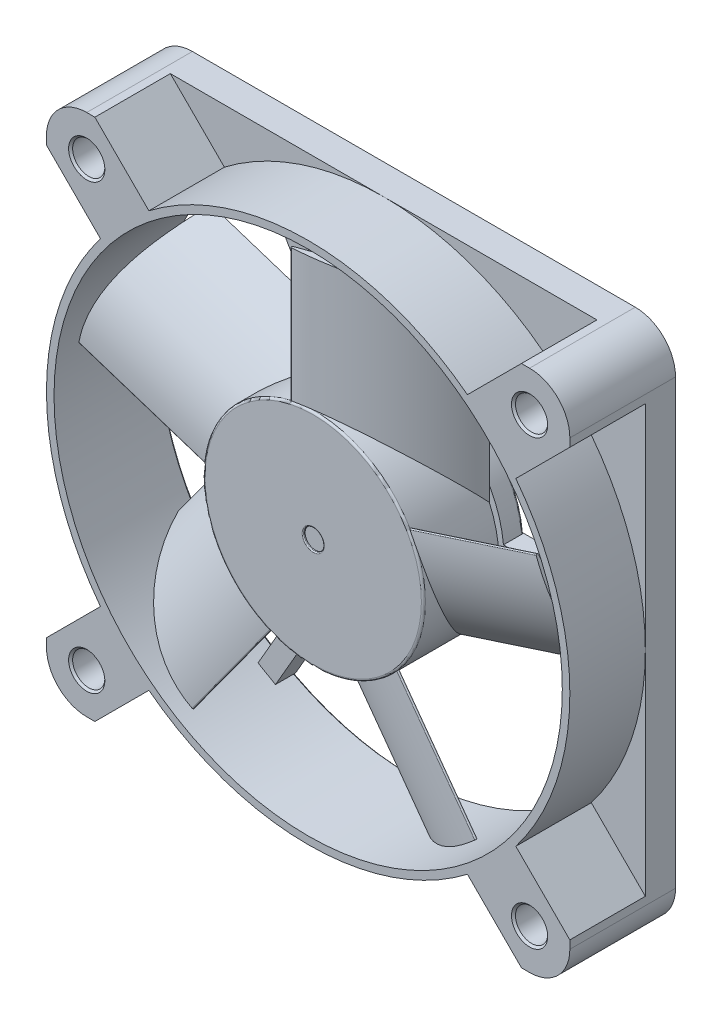
SolidWorks part; units mm, degrees
note: '?' marks a value the reader was unsure of.
material "ABS"
ref_plane "Спереди" through (0, 0, 0) normal (0, 0, 1) x (1, 0, 0)
ref_plane "Сверху" through (0, 0, 0) normal (0, 1, 0) x (1, 0, 0)
ref_plane "Справа" through (0, 0, 0) normal (1, 0, 0) x (0, 0, -1)
sketch "Эскиз1" plane through (0, 0, 0) normal (0, 0, 1) x (1, 0, 0)
  circle A0 centre (0, 0) radius 10.95
  dimension "D1" = 21.9
extrude "Вытянуть1" add sketch "Эскиз1" along normal blind 7.5
fillet "Скругление1" radius 0.2 1 edges at (10.95, 0, 7.5)
sketch "Эскиз2" plane through (0, 0, 7.5) normal (0, 0, 1) x (1, 0, 0)
  circle A0 centre (0, 0) radius 1
  dimension "D1" = 2
extrude "Вырез-Вытянуть1" cut sketch "Эскиз2" against normal blind 0.2
fillet "Скругление2" radius 0.1 1 edges at (1, 0, 7.5)
ref_plane "Плоскость1" through (0, 25, 0) normal (0, 1, 0) x (-1, 0, 0)
sketch "Эскиз3" plane through (0, 25, 0) normal (0, 1, 0) x (-1, 0, 0)
  line L0 (-10.95, 7.3) -> (10.95, 7.3) construction
  line L1 (-10.95, 0) -> (10.95, 0) construction
  arc A0 (2.2956, 7.3507) -> (-10, 0) centre (1.7146, -5.6363) ccw
  arc A1 (2.3134, 7.1533) -> (-10, 0) centre (7.6697, -16.2413) ccw
  arc A2 (2.2956, 7.3507) -> (2.3134, 7.1533) centre (2.2911, 7.2508) cw
  point P11 (3, 7.3)
  dimension "D3" = 13
  dimension "D4" = 24
  dimension "D5" = 0.1
  dimension "D1" = 13
  dimension "D2" = 3
extrude "Вытянуть2" add sketch "Эскиз3" against normal up to surface (14.2972 mm away)
ref_axis "Ось1" through (0, 0, 7.3) along (0, 0, -1)?
pattern_circular "Круговой массив1" count 5 over 360 about axis through (0, 0, 0) along (0, 0, 1) of "Вытянуть2"
sketch "Эскиз5" plane through (0, 0, 7.5) normal (0, 0, 1) x (1, 0, 0)
  circle A0 centre (0, 0) radius 24
  dimension "D1" = 48
extrude "Вырез-Вытянуть2" cut sketch "Эскиз5" against normal through all flip side to cut
ref_plane "Плоскость2" through (0, 0, -0.5) normal (0, 0, -1) x (-1, 0, 0)
sketch "Эскиз6" plane through (0, 0, -0.5) normal (0, 0, -1) x (-1, 0, 0)
  circle A0 centre (0, 0) radius 10.95
  arc A1 (-7.333, -8.132) -> (5.4679, -9.4871) centre (0, 0) ccw construction
extrude "Вытянуть3" add sketch "Эскиз6" along normal blind 2
fillet "Скругление3" radius 0.2 1 edges at (-10.95, 0, -2.5)
sketch "Эскиз7" plane through (0, 0, -2.5) normal (0, 0, -1) x (-1, 0, 0)
  circle A0 centre (0, 0) radius 26
  circle A1 centre (0, 0) radius 25.25
  dimension "D1" = 52
  dimension "D2" = 0.75
extrude "Вытянуть4" add sketch "Эскиз7" against normal blind 10.5
sketch "Эскиз8" plane through (0, 0, -2.5) normal (0, 0, -1) x (-1, 0, 0)
  line L0 (-22, 26) -> (22, 26)
  line L1 (26, 22) -> (26, -22)
  line L2 (22, -26) -> (-22, -26)
  line L3 (-26, -22) -> (-26, 22)
  arc A0 (22, 26) -> (26, 22) centre (22, 22) cw
  arc A1 (-22, 26) -> (-26, 22) centre (-22, 22) ccw
  arc A2 (-22, -26) -> (-26, -22) centre (-22, -22) cw
  arc A3 (26, -22) -> (22, -26) centre (22, -22) cw
  circle A4 centre (0, 0) radius 26
  point P7 (26, 26)
  point P10 (-26, 26)
  point P15 (26, -26)
  circle M2 centre (0, 0) radius 26
  dimension "D5" = 4
  dimension "D6" = 52
  dimension "D1" = 26
  dimension "D2" = 26
  dimension "D3" = 52
  dimension "D4" = 52
extrude "Вытянуть7" add sketch "Эскиз8" against normal blind 3 contours A2 L2 L3 M2 | A3 L1 L2 M2 | A0 L0 L1 M2 | L0 A1 L3 M2
sketch "Эскиз11" plane through (0, 0, -2.5) normal (0, 0, -1) x (-1, 0, 0)
  line L0 (15.2877, 20.096) -> (21.1917, 26)
  line L2 (20.096, 15.2877) -> (26, 21.1917)
  line L4 (0, 0) -> (22, 22) construction
  line L5 (21.1917, 26) -> (22, 26)
  line L6 (26, 21.1917) -> (26, 22)
  circle A0 centre (0, 0) radius 25.25 construction
  arc A1 (22, 26) -> (26, 22) centre (22, 22) cw
  arc A2 (15.2877, 20.096) -> (20.096, 15.2877) centre (0, 0) cw
  dimension "D1" = 3.4
  dimension "D2" = 6.8
extrude "Вытянуть8" add sketch "Эскиз11" against normal up to surface (10.5 mm away) up to face at (-25.25, 0, 8)
pattern_circular "Круговой массив2" count 4 over 360 about axis through (0, 0, 0) along (0, 0, 1) of "Вытянуть8"
sketch "Эскиз12" plane through (0, 0, -2.5) normal (0, 0, -1) x (-1, 0, 0)
  circle A0 centre (22, -22) radius 1.6
  circle A1 centre (22, 22) radius 1.6
  circle A2 centre (-22, 22) radius 1.6
  circle A3 centre (-22, -22) radius 1.6
  dimension "D1" = 3.2
  dimension "D2" = 3.2
  dimension "D3" = 3.2
  dimension "D4" = 3.2
extrude "Вырез-Вытянуть3" cut sketch "Эскиз12" against normal through all
sketch "Эскиз13" plane through (0, 0, -2.5) normal (0, 0, -1) x (-1, 0, 0)
  line L0 (0, -1) -> (-25.2302, -1)
  line L2 (-25.2302, -1) -> (-25.2302, 1)
  line L3 (-25.2302, 1) -> (0, 1)
  line L4 (0, 1) -> (0, -1)
  line L5 (-0.866, 0.5) -> (11.7491, 22.35)
  line L6 (11.7491, 22.35) -> (13.4811, 21.35)
  line L7 (13.4811, 21.35) -> (0.866, -0.5)
  line L8 (0.866, -0.5) -> (-0.866, 0.5)
  line L9 (0.866, 0.5) -> (13.4811, -21.35)
  line L10 (13.4811, -21.35) -> (11.7491, -22.35)
  line L11 (11.7491, -22.35) -> (-0.866, -0.5)
  line L12 (-0.866, -0.5) -> (0.866, 0.5)
  circle A0 centre (0, 0) radius 25.25 construction
  circle M1 centre (0, 0) radius 10.75
  dimension "D1" = 2
  dimension "D2" = 1
extrude "Вытянуть9" add sketch "Эскиз13" against normal blind 2 contours L3 L2 L0 M1 | L7 L6 L5 M1 | L11 L10 L9 M1
chamfer "Фаска1" distance 0.2 angle 45 9 edges at (20.4, -22, 8) (-23.6, -22, 8) (20.4, 22, 8) (-23.6, 22, 8) (-25.25, 0, -2.5) (20.4, -22, -2.5) (-23.6, -22, -2.5) (20.4, 22, -2.5) (-23.6, 22, -2.5)
